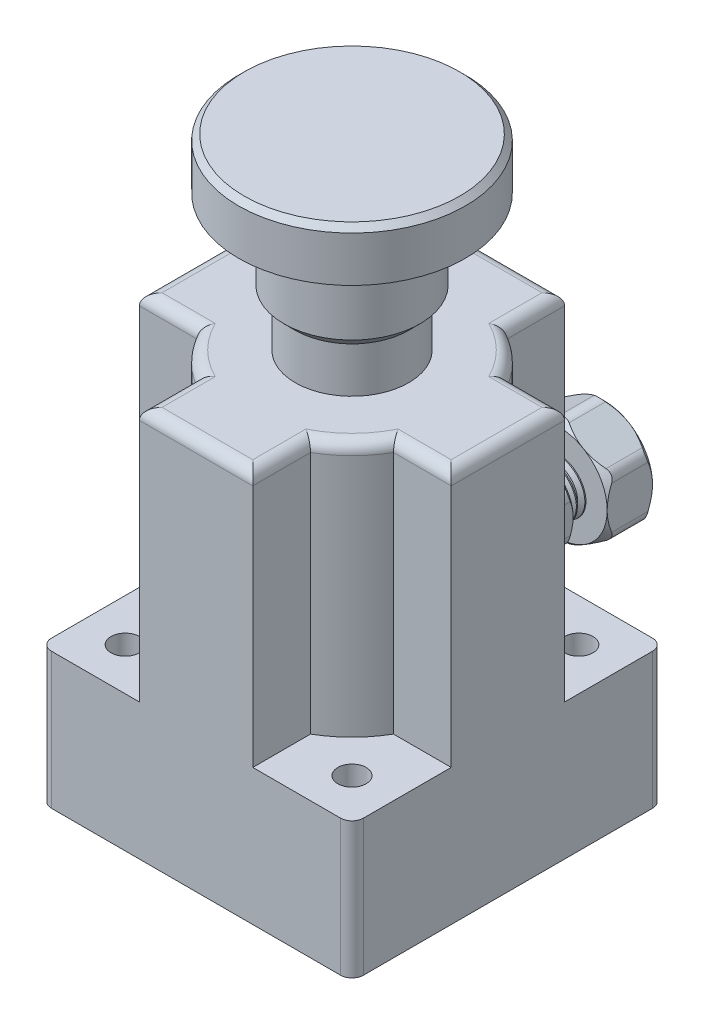
SolidWorks part; units mm, degrees
ref_plane "前视基准面" through (0, 0, 0) normal (0, 0, 1) x (1, 0, 0)
ref_plane "上视基准面" through (0, 0, 0) normal (0, 1, 0) x (1, 0, 0)
ref_plane "右视基准面" through (0, 0, 0) normal (1, 0, 0) x (0, 0, -1)
sketch "草图1" plane through (0, 0, 0) normal (0, 1, 0) x (1, 0, 0)
  line L1 (-27.5, 27.5) -> (27.5, 27.5)
  line L2 (-27.5, 27.5) -> (-27.5, -27.5)
  line L3 (-27.5, -27.5) -> (27.5, -27.5)
  line L4 (27.5, 27.5) -> (27.5, -27.5)
  line L5 (-27.5, 27.5) -> (27.5, -27.5) construction
  line L6 (-27.5, -27.5) -> (27.5, 27.5) construction
  line L7 (-20, 20) -> (20, 20) construction
  line L8 (-20, 20) -> (-20, -20) construction
  line L9 (-20, -20) -> (20, -20) construction
  line L10 (20, 20) -> (20, -20) construction
  line L11 (-20, 20) -> (20, -20) construction
  line L12 (-20, -20) -> (20, 20) construction
  circle A0 centre (-20, 20) radius 2.5
  circle A1 centre (20, 20) radius 2.5
  circle A2 centre (20, -20) radius 2.5
  circle A3 centre (-20, -20) radius 2.5
  circle A4 centre (0, 0) radius 18 construction
  circle A5 centre (0, 18) radius 2
  circle A6 centre (18, 0) radius 2
  circle A7 centre (0, -18) radius 2
  circle A8 centre (-18, 0) radius 2
  point P0 (0, 0)
  point P6 (0, 0)
  dimension "D2" = 5
  dimension "D4" = 4
  dimension "D5" = 36
  dimension "D1" = 55
  dimension "D3" = 40
extrude "凸台-拉伸1" add sketch "草图1" along normal blind 24
sketch "草图2" plane through (0, 24, 0) normal (0, 1, 0) x (1, 0, 0)
  line L0 (-29.6425, 0) -> (28.7053, 0) construction
  line L1 (0, 29.0177) -> (0, -29.3301) construction
  line L2 (-10, 27.5) -> (-10, 17.3205)
  line L3 (27.5, 27.5) -> (-27.5, 27.5) construction
  line L4 (-17.3205, 10) -> (-27.5, 10)
  line L5 (-27.5, 27.5) -> (-27.5, -27.5) construction
  line L6 (-10, 27.5) -> (10, 27.5)
  line L7 (-27.5, 10) -> (-27.5, -10)
  line L8 (-17.3205, -10) -> (-27.5, -10)
  line L9 (-10, -27.5) -> (-10, -17.3205)
  line L10 (10, -27.5) -> (10, -17.3205)
  line L11 (17.3205, -10) -> (27.5, -10)
  line L12 (27.5, 10) -> (27.5, -10)
  line L13 (17.3205, 10) -> (27.5, 10)
  line L14 (10, 27.5) -> (10, 17.3205)
  line L15 (-17.3205, 10) -> (-17.3205, -10) construction
  line L16 (-10, -17.3205) -> (10, -17.3205) construction
  line L17 (17.3205, -10) -> (17.3205, 10) construction
  line L19 (-10, -27.5) -> (10, -27.5)
  arc A0 (-17.3205, -10) -> (-10, -17.3205) centre (0, 0) ccw
  arc A1 (10, -17.3205) -> (17.3205, -10) centre (0, 0) ccw
  arc A2 (17.3205, 10) -> (10, 17.3205) centre (0, 0) ccw
  arc A3 (-10, 17.3205) -> (-17.3205, 10) centre (0, 0) ccw
  point P17 (-27.5, 0)
  point P24 (0, 27.5)
  point P25 (27.5, 0)
  dimension "D2" = 40
  dimension "D1" = 10
extrude "凸台-拉伸2" add sketch "草图2" along normal blind 45
sketch "草图3" plane through (0, 0, 0) normal (0, 0, 1) x (1, 0, 0)
  line L0 (0, 121.3602) -> (0, -8.0143) construction
  line L1 (-10, 69) -> (-10, 77)
  line L2 (-10, 69) -> (10, 69) construction
  line L3 (-10, 77) -> (-12, 79)
  line L4 (-12, 79) -> (-12, 93)
  line L5 (-12, 93) -> (-20, 93)
  line L6 (-20, 93) -> (-20, 101)
  line L7 (-20, 101) -> (-19, 102)
  line L8 (-19, 102) -> (0, 102)
  line L9 (-27.5, 0) -> (27.5, 0) construction
  line L10 (0, 102) -> (0, 69)
  line L11 (-10, 69) -> (0, 69)
  dimension "D1" = 20
  dimension "D2" = 8
  dimension "D3" = 1
  dimension "D4" = 135
  dimension "D5" = 2
  dimension "D6" = 102
  dimension "D7" = 8
  dimension "D8" = 8
revolve "旋转1" add sketch "草图3" angle 360 about L0
sketch "草图4" plane through (0, 0, -27.5) normal (0, 0, -1) x (-1, 0, 0)
  line L0 (0, 44.6226) -> (0, -17.2797) construction
  line L1 (-34.2331, 30.5) -> (38.6763, 30.5) construction
  line L2 (-27.5, 0) -> (27.5, 0) construction
  line L3 (0, 38.0056) -> (-6.5, 34.2528)
  line L4 (-6.5, 34.2528) -> (-6.5, 26.7472)
  line L5 (-6.5, 26.7472) -> (0, 22.9944)
  line L6 (0, 22.9944) -> (6.5, 26.7472)
  line L7 (6.5, 26.7472) -> (6.5, 34.2528)
  line L8 (6.5, 34.2528) -> (0, 38.0056)
  circle A0 centre (0, 30.5) radius 6.5 construction
  dimension "D1" = 30.5
  dimension "D2" = 13
extrude "凸台-拉伸3" add sketch "草图4" along normal blind 5
sketch "草图5" plane through (0, 0, -32.5) normal (0, 0, -1) x (-1, 0, 0)
  line L0 (-6.5, 34.2528) -> (6.5, 26.7472) construction
  line L1 (6.5, 34.2528) -> (-6.5, 26.7472) construction
  circle A0 centre (0, 30.5) radius 5
  dimension "D1" = 10
extrude "凸台-拉伸4" add sketch "草图5" along normal blind 12
thread "螺纹线1" pitch 1.5 method cut profile "螺纹线轮廓1" start angle 0, offset 0, length 15, pitch 1.5, diameter 10
ref_plane "基准面1" through (-5, 30.5, -32.5) normal (0, -1, 0) x (-1, 0, 0)
sketch "螺纹线轮廓1" plane through (-5, 30.5, -32.5) normal (0, -1, 0) x (-1, 0, 0)
  line L0 (0, 0) -> (0, 1.5) construction
  line L11 (0, 0) -> (0, 1.3125)
  line L12 (0, 1.3125) -> (-0.8119, 0.8437)
  line L13 (-0.8119, 0.8437) -> (-0.8119, 0.4687)
  line L15 (-0.8119, 0.4687) -> (0, 0)
  line L17 (-0.8119, 0.6562) -> (0, 0.6562) construction
  point P2 (0, 0)
  dimension "Pitch" = 1.5
  dimension "Profile_Angle" = 60
  dimension "Profile_Land" = 0.375
  dimension "Profile_Height" = 0.8119
sketch "草图9" plane through (0, 0, -44.5) normal (0, 0, -1) x (-1, 0, 0)
  line L0 (0, 38.0056) -> (0, 22.9944) construction
  line L1 (-6.5, 30.5) -> (6.5, 30.5) construction
  line L2 (-6.5, 34.2528) -> (-6.5, 26.7472) construction
  line L3 (6.5, 26.7472) -> (6.5, 34.2528) construction
  line L5 (0, 20.685) -> (8.5, 25.5925)
  line L6 (8.5, 25.5925) -> (8.5, 35.4075)
  line L7 (8.5, 35.4075) -> (0, 40.315)
  line L8 (0, 40.315) -> (-8.5, 35.4075)
  line L9 (-8.5, 35.4075) -> (-8.5, 25.5925)
  line L10 (-8.5, 25.5925) -> (0, 20.685)
  circle A0 centre (0, 30.5) radius 8.5 construction
  dimension "D1" = 17
extrude "凸台-拉伸5" add sketch "草图9" against normal blind 8
fillet "圆角1" radius 2 12 edges at (-6.5, 26.7472, -30) (-6.5, 34.2528, -30) (0, 38.0056, -30) (0, 40.315, -40.5) (-8.5, 35.4075, -40.5) (-8.5, 25.5925, -40.5) (0, 20.685, -40.5) (8.5, 35.4075, -40.5) (8.5, 25.5925, -40.5) (0, 22.9944, -30) (6.5, 34.2528, -30) (6.5, 26.7472, -30)
sketch "草图12" plane through (0, 0, 0) normal (1, 0, 0) x (0, 0, -1)
  line L0 (-35.114, 30.5) -> (71.1706, 30.5) construction
  line L1 (-27.5, 0) -> (27.5, 0) construction
  line L2 (43.4944, 40.0056) -> (44.5, 39)
  line L3 (44.5, 40.0056) -> (36.5, 40.0056) construction
  line L4 (44.5, 39.7376) -> (44.5, 35.9848) construction
  line L5 (44.5, 39) -> (44.5, 40.0056)
  line L6 (44.5, 39.7376) -> (44.5, 40.0056) construction
  line L7 (44.5, 40.0056) -> (43.4944, 40.0056)
  line L8 (40.5, 43.2643) -> (40.5, 18.7075) construction
  line L9 (36.5, 39.7376) -> (36.5, 35.9848) construction
  line L10 (36.5, 40.0056) -> (37.5056, 40.0056)
  line L11 (36.5, 39) -> (36.5, 40.0056)
  line L12 (37.5056, 40.0056) -> (36.5, 39)
  line L13 (31.8038, 37.6962) -> (32.5, 37.6962)
  line L14 (32.5, 37.6962) -> (27.5, 37.6962) construction
  line L15 (32.5, 37.6962) -> (32.5, 37)
  line L16 (32.5, 37.4282) -> (32.5, 34.8301) construction
  line L17 (32.5, 37) -> (31.8038, 37.6962)
  dimension "D1" = 30.5
  dimension "D2" = 8.5
  dimension "D3" = 6.5
revolve "切除-旋转1" cut sketch "草图12" angle 360 about L0
fillet "圆角2" radius 2 21 edges at (0, 93, 12) (10, 69, -22.4103) (14.1421, 69, -14.1421) (22.4103, 69, -10) (22.4103, 69, 10) (14.1421, 69, 14.1421) (10, 69, 22.4103) (0, 69, 27.5) (-10, 69, 22.4103) (-14.1421, 69, 14.1421) (-22.4103, 69, 10) (-27.5, 69, 0) (-22.4103, 69, -10) (-14.1421, 69, -14.1421) (-10, 69, -22.4103) (0, 69, -27.5) (27.5, 69, 0) (27.5, 12, 27.5) (27.5, 12, -27.5) (-27.5, 12, 27.5) (-27.5, 12, -27.5)
ref_plane "基准面2" through (0, 93.5, 0) normal (0, -1, 0) x (-1, 0, 0)
sketch "草图13" plane through (0, 93.5, 0) normal (0, -1, 0) x (1, 0, 0)
  circle A0 centre (0, 0) radius 19
  dimension "D1" = 38
extrude "凸台-拉伸6" add sketch "草图13" against normal blind 1 separate body
sketch "草图14" plane through (0, 94.5, 0) normal (0, 1, 0) x (1, 0, 0)
  circle A0 centre (0, 0) radius 1
  dimension "D1" = 2
extrude "凸台-拉伸7" add sketch "草图14" along normal blind 2
sketch "草图15" plane through (0, 96.5, 0) normal (0, 1, 0) x (1, 0, 0)
  line L0 (0, 0) -> (11.5641, 11.5641) construction
  line L1 (-20.8952, 0) -> (22.6972, 0) construction
  line L2 (0.7807, 1.8413) -> (7.8517, 8.9124)
  line L3 (7.8517, 8.9124) -> (6.7911, 9.9731)
  line L4 (6.7911, 9.9731) -> (11.5641, 11.5641)
  line L5 (9.9731, 6.7911) -> (11.5641, 11.5641)
  line L6 (8.9124, 7.8517) -> (9.9731, 6.7911)
  line L7 (1.8413, 0.7807) -> (8.9124, 7.8517)
  circle A0 centre (0, 0) radius 2
  point P4 (12.7994, 12.7994)
  point P8 (12.5243, 12.5243)
  point P11 (0, 0)
  point P12 (0, 0)
  circle M6 centre (0, 0) radius 1
  dimension "D1" = 4
  dimension "D2" = 45
  dimension "D3" = 0.75
  dimension "D4" = 1.5
  dimension "D5" = 4.5
  dimension "D6" = 10
extrude "凸台-拉伸8" add sketch "草图15" along normal blind 2 contours A0 L7 L6 L5 L4 L3 L2 | A0 M6 | M6 region at (6.7302, 96.5, -6.7302) region at (1.3742, 96.5, -1.3742) region at (0, 96.5, 0)
sketch "草图16" plane through (0, 98.5, 0) normal (0, 1, 0) x (1, 0, 0)
  circle A0 centre (0, 0) radius 1
  dimension "D1" = 2
extrude "凸台-拉伸9" add sketch "草图16" along normal blind 2
chamfer "倒角1" distance 1 angle 45 1 edges at (0, 100.5, 1)
